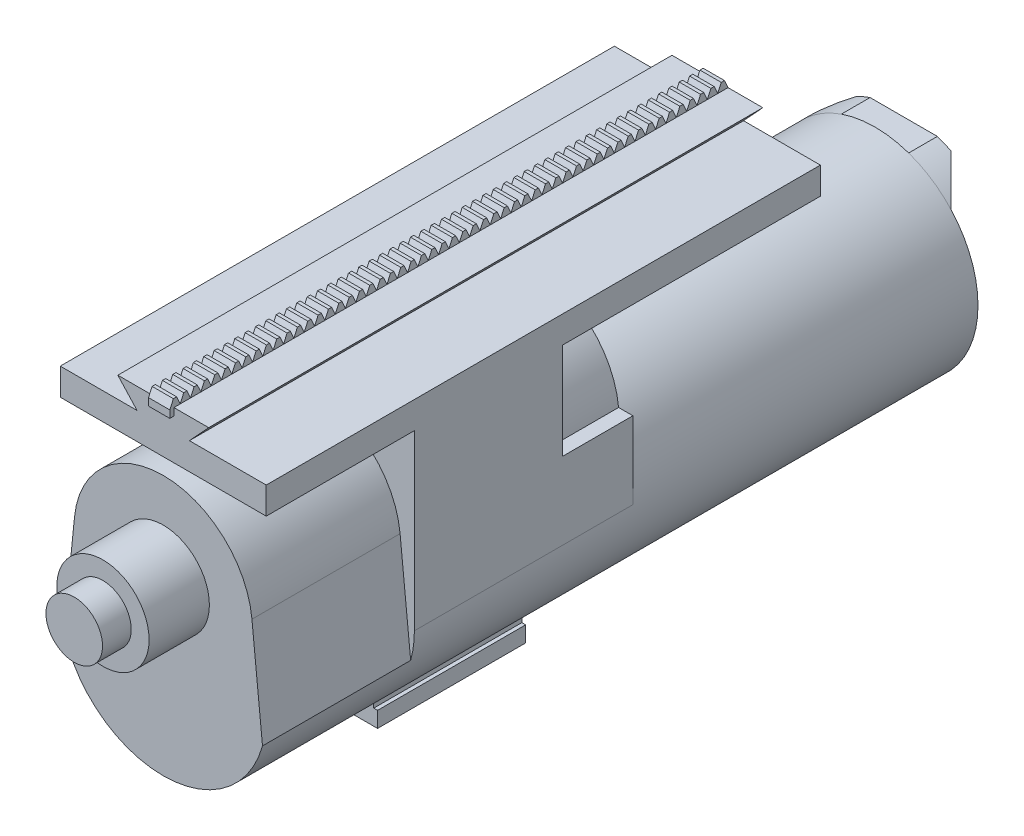
SolidWorks part; units mm, degrees
ref_plane "Front" through (0, 0, 0) normal (0, 0, 1) x (1, 0, 0)
ref_plane "Top" through (0, 0, 0) normal (0, 1, 0) x (1, 0, 0)
ref_plane "Right" through (0, 0, 0) normal (1, 0, 0) x (0, 0, -1)
sketch "Sketch1" plane through (0, 0, 0) normal (0, 0, 1) x (1, 0, 0)
  line L0 (0, 25.0236) -> (0, -25.0236)
  arc A0 (0, -25.0236) -> (0, 25.0236) centre (0, 0) ccw
extrude "Boss-Extrude1" add sketch "Sketch1" against normal blind 25.4
sketch "Sketch2" plane through (0, 0, -25.4) normal (0, 0, -1) x (-1, 0, 0)
  line L0 (0, 40.8152) -> (0, -40.8152)
  arc A0 (0, 40.8152) -> (0, -40.8152) centre (0, 0) ccw
extrude "Boss-Extrude2" add sketch "Sketch2" along normal blind 53.34
sketch "Sketch3" plane through (0, 0, -78.74) normal (0, 0, -1) x (-1, 0, 0)
  line L0 (0, 0) -> (0, -84.5066) construction
  line L2 (-87.8058, -84.5066) -> (-78.4751, 7.9221)
  line L5 (0, 78.874) -> (0, -151.3045)
  line L6 (0, -84.5066) -> (-87.8058, -84.5066) construction
  arc A1 (-87.8058, -84.5066) -> (0, -151.3045) centre (0, -60.1951) ccw
  arc A2 (0, 78.874) -> (-78.4751, 7.9221) centre (0, 0) ccw
  point P7 (0, -84.5066)
extrude "Boss-Extrude4" add sketch "Sketch3" along normal blind 131.064
sketch "Sketch4" plane through (0, 0, -209.804) normal (0, 0, -1) x (-1, 0, 0)
  line L0 (-91.1093, 93.1756) -> (0, 93.1756)
  line L1 (-91.1093, -60.1951) -> (-91.1093, 93.1756)
  line L3 (-58.5221, -151.3045) -> (0, -151.3045)
  line L4 (-58.5221, -151.3045) -> (-58.5221, -137.4246)
  line L5 (-58.5221, -137.4246) -> (-55.1541, -137.4246)
  line L6 (-55.1541, -137.4246) -> (-55.1541, -132.7137)
  line L11 (0, 93.1756) -> (0, -151.3045)
  arc A1 (-87.8058, -84.5066) -> (0, -151.3045) centre (0, -60.1951) ccw construction
  arc A2 (-91.1093, -60.1951) -> (-55.1541, -132.7137) centre (0, -60.1951) ccw
  point P1 (0, 78.874)
  point P3 (-45.5547, 93.1756)
  point P6 (0, 0)
  point P8 (0, -151.3045)
  point P14 (0, -151.3045)
extrude "Boss-Extrude5" add sketch "Sketch4" along normal blind 131.064
sketch "Sketch5" plane through (0, 0, -340.868) normal (0, 0, -1) x (-1, 0, 0)
  line L0 (-91.1093, -60.1951) -> (-91.1093, 7.9221)
  line L2 (-91.1093, 7.9221) -> (-78.4751, 7.9221)
  line L4 (-91.1093, 7.9221) -> (-91.1093, -60.1951)
  line L5 (0, 78.874) -> (0, -151.3045)
  arc A1 (0, 78.874) -> (-78.4751, 7.9221) centre (0, 0) ccw construction
  arc A3 (0, 78.874) -> (-78.4751, 7.9221) centre (0, 0) ccw
  arc A5 (-91.1093, -60.1951) -> (-55.1541, -132.7137) centre (0, -60.1951) ccw construction
  arc A6 (-91.1093, -60.1951) -> (0, -151.3045) centre (0, -60.1951) ccw
  line M9 (-91.1093, 93.1756) -> (-91.1093, -60.1951)
  arc M10 (-91.1093, -60.1951) -> (-55.1541, -132.7137) centre (0, -60.1951) ccw
extrude "Boss-Extrude6" add sketch "Sketch5" along normal blind 62.23 contours A3 L2 M9 M10 region at (39.6645, -38.0067, -340.868)
sketch "Sketch6" plane through (0, 0, -403.098) normal (0, 0, -1) x (-1, 0, 0)
  line L0 (0, -151.3045) -> (0, 30.9142)
  arc A0 (0, 30.9142) -> (0, -151.3045) centre (0, -60.1951) ccw
  arc A1 (-91.1093, -60.1951) -> (0, -151.3045) centre (0, -60.1951) ccw construction
extrude "Boss-Extrude7" add sketch "Sketch6" along normal blind 305.308
sketch "Sketch7" plane through (0, 0, -708.406) normal (0, 0, -1) x (-1, 0, 0)
  line L1 (-67.3495, 1.1641) -> (0, 1.1641) construction
  line L2 (-67.3495, 1.1641) -> (-67.3495, -121.5543)
  line L3 (-67.3495, -121.5543) -> (0, -121.5543)
  line L5 (-67.3495, 1.1641) -> (0, -60.1951) construction
  line L6 (-67.3495, -121.5543) -> (0, -60.1951) construction
  line L7 (-29.7719, 25.9126) -> (0, 25.9126)
  line L8 (0, -151.3045) -> (0, 30.9142)
  line L9 (0, -124.6192) -> (0, 25.9126)
  arc A2 (0, 30.9142) -> (0, -151.3045) centre (0, -60.1951) ccw
  arc A3 (-29.7719, 25.9126) -> (-67.3495, 1.1641) centre (0, -60.1951) ccw
  point P0 (0, -60.1951)
  point P11 (67.3495, -121.5543)
  arc M5 (0, 30.9142) -> (0, -151.3045) centre (0, -60.1951) ccw
  line M9 (0, -151.3045) -> (0, 30.9142)
  dimension "D1" = 0
extrude "Boss-Extrude8" add sketch "Sketch7" along normal blind 25.4 contours L7 L2 L3 M5 M9 region at (32.783, -50.455, -708.406)
ref_plane "Plane1" through (0, 0, -708.406) normal (0, 0, -1) x (-1, 0, 0)
split line "Split Line1"
chamfer "Chamfer1" distance 25.4 2 edges at (33.6748, -121.5543, -733.806) (67.3495, -60.1951, -733.806)
ref_plane "Plane2" through (0, 0, -78.74) normal (0, 0, 1) x (1, 0, 0)
sketch "Sketch9" plane through (0, 0, -78.74) normal (0, 0, 1) x (1, 0, 0)
  line L0 (0, 93.1756) -> (91.1093, 93.1756)
  line L1 (91.1093, 93.1756) -> (91.1093, 117.0242)
  line L2 (91.1093, 117.0242) -> (23.1442, 117.0242)
  line L3 (23.1442, 117.0242) -> (40.1756, 135.524)
  line L4 (40.1756, 135.524) -> (9.4233, 135.524)
  line L5 (9.4233, 135.524) -> (9.4233, 129.0233)
  line L6 (9.4233, 129.0233) -> (0, 129.0233)
  line L7 (0, 129.0233) -> (0, 93.1756)
  point P4 (58.0659, 121.2224)
  point P11 (-69.8667, 93.1756)
extrude "Boss-Extrude10" add sketch "Sketch9" against normal blind 490.22
sketch "Sketch10" plane through (9.4233, 0, 0) normal (-1, 0, 0) x (0, 0, 1)
  line L0 (-568.96, 129.0233) -> (-568.96, 135.524)
  line L1 (-568.96, 135.524) -> (-565.7924, 142.5581)
  line L2 (-565.7924, 142.5581) -> (-562.9296, 142.5581)
  line L3 (-562.9296, 142.5581) -> (-559.762, 135.524)
  line L4 (-568.96, 135.524) -> (-78.74, 135.524) construction
  line L5 (-559.762, 135.524) -> (-559.762, 129.0233)
  line L6 (-568.96, 129.0233) -> (-78.74, 129.0233) construction
  line L7 (-559.762, 129.0233) -> (-568.96, 129.0233)
  point P4 (-561.2696, 137.6131)
  point P13 (-565.7481, 138.5819)
  point P14 (-564.361, 142.5581)
  point P15 (-564.361, 129.0233)
  point P16 (-565.7924, 142.5581)
extrude "Boss-Extrude11" add sketch "Sketch10" along normal up to surface (9.4233 mm away) up to face at (0, 8.4633, -302.5503)
pattern_linear "LPattern1" count 54 spacing 9.144 along (0, 0, 1) of "Boss-Extrude11"
sketch "Sketch11" plane through (0, -151.3045, 0) normal (0, -1, 0) x (1, 0, 0)
  line L0 (34.9826, -209.804) -> (20.7145, -340.868)
  line L1 (47.4381, -209.804) -> (47.4381, -340.868) construction
  line L2 (34.9826, -209.804) -> (0, -209.804)
  line L3 (0, -209.804) -> (0, -340.868)
  line L4 (58.5221, -209.804) -> (0, -209.804)
  line L5 (0, -209.804) -> (0, -340.868)
  line L6 (0, -340.868) -> (58.5221, -340.868)
  line L7 (58.5221, -340.868) -> (58.5221, -209.804)
  line L8 (58.5221, -209.804) -> (34.9826, -209.804)
  line L10 (20.7145, -340.868) -> (58.5221, -340.868)
  line L11 (58.5221, -340.868) -> (58.5221, -209.804)
  line L12 (0, -340.868) -> (20.7145, -340.868)
  circle A0 centre (47.4381, -226.7149) radius 7.2286
  circle A1 centre (47.4381, -328.6293) radius 7.2286
  line M8 (58.5221, -209.804) -> (0, -209.804)
  line M9 (0, -209.804) -> (0, -340.868)
  line M10 (0, -340.868) -> (58.5221, -340.868)
  dimension "D1" = 0
extrude "Cut-Extrude1" cut sketch "Sketch11" against normal up to surface contours L0 M8 M9 M10 region at (14.2289, -151.3045, -269.7401) up to face at (46.3513, -80.0864, -401.7772)
extrude "Cut-Extrude2" cut sketch "Sketch11<3>" against normal blind 6.35 contours A0 L1 | L1 A0 | A1 L1 | L1 A1 region at (50.506, -151.3045, -226.7149) region at (44.3702, -151.3045, -226.7149) region at (44.3702, -151.3045, -328.6293) region at (50.506, -151.3045, -328.6293)
sketch "Sketch11<3>" plane through (0, -151.3045, 0) normal (0, -1, 0) x (1, 0, 0) same geometry as "Sketch11"
mirror "Mirror1" about plane through (0, 25.0236, -25.4) normal (-1, 0, 0) of bodies 114
